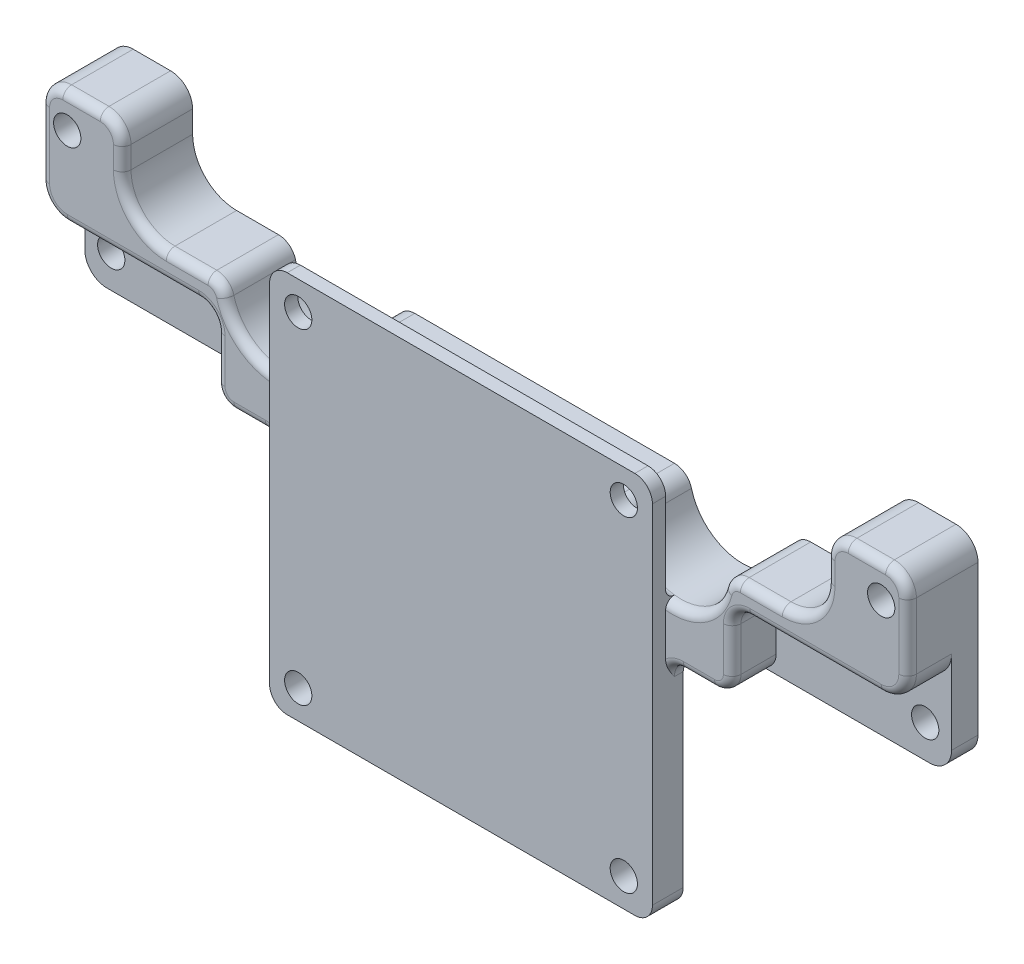
SolidWorks part; units mm, degrees
ref_plane "Front Plane" through (0, 0, 0) normal (0, 0, 1) x (1, 0, 0)
ref_plane "Top Plane" through (0, 0, 0) normal (0, 1, 0) x (1, 0, 0)
ref_plane "Right Plane" through (0, 0, 0) normal (1, 0, 0) x (0, 0, -1)
sketch "Sketch2" plane through (0, 0, 0) normal (0, 0, 1) x (1, 0, 0)
  line L0 (0, 11) -> (0, 0) construction
  line L1 (-49.25, -11) -> (49.25, -11)
  line L2 (-49.25, -11) -> (-49.25, 11)
  line L3 (-49.25, 11) -> (-40, 11)
  line L5 (-49.25, -11) -> (49.25, 11) construction
  line L6 (-49.25, 11) -> (49.25, -11) construction
  line L7 (-49.25, 0) -> (0, 0) construction
  line L8 (-46.25, 9.25) -> (-46.25, -9.25) construction
  line L9 (40, 1) -> (-40, 1)
  line L10 (-40, 1) -> (-40, 11)
  line L11 (0, 1) -> (0, 0)
  line L12 (49.25, -11) -> (49.25, 11)
  line L13 (49.25, 11) -> (40, 11)
  line L14 (40, 1) -> (40, 11)
  circle A0 centre (-46.25, 7.25) radius 2
  circle A1 centre (-46.25, -7.25) radius 2
  circle A2 centre (46.25, 7.25) radius 2
  circle A3 centre (46.25, -7.25) radius 2
  point P0 (0, 0)
  dimension "D4" = 4
  dimension "D1" = 98.5
  dimension "D2" = 22
  dimension "D3" = 18.5
  dimension "D5" = 9.25
  dimension "D6" = 3
  dimension "D7" = 40
  dimension "D8" = 10
extrude "Boss-Extrude1" add sketch "Sketch2" along normal blind 8 contours L12 L13 L14 L9 L10 L3 L2 L1 | A1 | A0 | A3 | A2
fillet "Fillet1" radius 2.5 4 edges at (-49.25, 11, 4) (-49.25, -11, 4) (49.25, 11, 4) (49.25, -11, 4)
fillet "Fillet2" radius 2.5 2 edges at (-40, 11, 4) (40, 11, 4)
fillet "Fillet3" radius 5 2 edges at (-40, 1, 4) (40, 1, 4)
sketch "Sketch4" plane through (0, 0, 8) normal (0, 0, 1) x (1, 0, 0)
  line L0 (0, -11) -> (0, 1) construction
  line L1 (-46.75, -11) -> (46.75, -11) construction
  line L2 (35, 1) -> (-35, 1) construction
  circle A0 centre (-22.5, 1) radius 6
  circle A1 centre (22.5, 1) radius 6
  dimension "D2" = 12
  dimension "D1" = 45
extrude "Cut-Extrude1" cut sketch "Sketch4" against normal blind 3
fillet "Fillet4" radius 2 4 edges at (-16.5, 1, 6.5) (16.5, 1, 6.5) (28.5, 1, 6.5) (-28.5, 1, 6.5)
sketch "Sketch6" plane through (0, 0, 8) normal (0, 0, 1) x (1, 0, 0)
  line L0 (-46.25, 7.25) -> (46.25, 7.25) construction
  line L1 (0, 7.25) -> (0, -14.5) construction
  line L3 (21.75, -36.25) -> (-21.75, -36.25)
  line L4 (21.75, -36.25) -> (21.75, 7.25)
  line L5 (21.75, 7.25) -> (-21.75, 7.25)
  line L6 (-21.75, -36.25) -> (-21.75, 7.25)
  line L7 (21.75, -36.25) -> (-21.75, 7.25) construction
  line L8 (21.75, 7.25) -> (-21.75, -36.25) construction
  dimension "D2" = 43.5
  dimension "D3" = 43.5
extrude "Boss-Extrude2" add sketch "Sketch6" along normal blind 1.5
sketch "Sketch8" plane through (0, 0, 5) normal (0, 0, 1) x (1, 0, 0)
  line L1 (30.246, 1) -> (14.754, 1)
  line L2 (30.246, 1) -> (14.754, 1)
  line L3 (-14.754, 1) -> (-30.246, 1)
  line L4 (-14.754, 1) -> (-30.246, 1)
  arc A3 (16.6905, -0.5) -> (14.754, 1) centre (14.754, -1) ccw
  arc A4 (16.6905, -0.5) -> (28.3095, -0.5) centre (22.5, 1) ccw
  arc A5 (30.246, 1) -> (28.3095, -0.5) centre (30.246, -1) ccw
  arc A6 (16.6905, -0.5) -> (14.754, 1) centre (14.754, -1) ccw
  arc A7 (16.6905, -0.5) -> (28.3095, -0.5) centre (22.5, 1) ccw
  arc A8 (30.246, 1) -> (28.3095, -0.5) centre (30.246, -1) ccw
  arc A9 (-28.3095, -0.5) -> (-30.246, 1) centre (-30.246, -1) ccw
  arc A10 (-28.3095, -0.5) -> (-16.6905, -0.5) centre (-22.5, 1) ccw
  arc A11 (-14.754, 1) -> (-16.6905, -0.5) centre (-14.754, -1) ccw
  arc A12 (-28.3095, -0.5) -> (-30.246, 1) centre (-30.246, -1) ccw
  arc A13 (-28.3095, -0.5) -> (-16.6905, -0.5) centre (-22.5, 1) ccw
  arc A14 (-14.754, 1) -> (-16.6905, -0.5) centre (-14.754, -1) ccw
  dimension "D1" = 0
  dimension "D2" = 0
extrude "Cut-Extrude2" cut sketch "Sketch8" against normal through all
sketch "Sketch7" plane through (0, 0, 9.5) normal (0, 0, 1) x (1, 0, 0)
  line L0 (0, 7.25) -> (0, -36.25) construction
  line L1 (21.75, 7.25) -> (-21.75, 7.25) construction
  line L2 (-21.75, -36.25) -> (21.75, -36.25) construction
  line L4 (18.5, -33) -> (-18.5, -33) construction
  line L5 (18.5, -33) -> (18.5, 4) construction
  line L6 (18.5, 4) -> (-18.5, 4) construction
  line L7 (-18.5, -33) -> (-18.5, 4) construction
  line L8 (18.5, -33) -> (-18.5, 4) construction
  line L9 (18.5, 4) -> (-18.5, -33) construction
  circle A0 centre (-18.5, 4) radius 1.55
  circle A1 centre (18.5, 4) radius 1.55
  circle A2 centre (18.5, -33) radius 1.55
  circle A3 centre (-18.5, -33) radius 1.55
  point P6 (0, -14.5)
  dimension "D3" = 3.1
  dimension "D1" = 37
  dimension "D2" = 37
extrude "Cut-Extrude3" cut sketch "Sketch7" against normal through all
sketch "Sketch9" plane through (0, 0, 8) normal (0, 0, -1) x (-1, 0, 0)
  line L4 (21.75, -36.25) -> (21.75, -11)
  line L5 (21.75, -11) -> (-21.75, -11)
  line L6 (-21.75, -11) -> (-21.75, -36.25)
  line L7 (-21.75, -36.25) -> (21.75, -36.25)
  line L8 (21.75, -36.25) -> (21.75, -11)
  line L9 (21.75, -11) -> (-21.75, -11)
  line L10 (-21.75, -11) -> (-21.75, -36.25)
  line L11 (-21.75, -36.25) -> (21.75, -36.25)
  circle A0 centre (18.5, -33) radius 1.55 construction
  circle A1 centre (-18.5, -33) radius 1.55 construction
  circle A2 centre (18.5, -33) radius 1.55
  circle A3 centre (-18.5, -33) radius 1.55
  dimension "D1" = 0
extrude "Boss-Extrude3" add sketch "Sketch9" along normal blind 2
fillet "Fillet5" radius 2 3 edges at (-21.75, -11, 7) (21.75, -11, 7) (0, -11, 6)
sketch "Sketch11" plane through (0, 0, 8) normal (0, 0, 1) x (1, 0, 0)
  line L1 (53.3142, -14.1394) -> (29.3142, -14.1394)
  line L2 (53.3142, -14.1394) -> (53.3142, -2.0055)
  line L3 (53.3142, -2.0055) -> (29.3142, -2.0055)
  line L4 (29.3142, -14.1394) -> (29.3142, -2.0055)
  dimension "D1" = 24
extrude "Cut-Extrude4" cut sketch "Sketch11" against normal blind 5
fillet "Fillet6" radius 2 2 edges at (29.3142, -11, 5.5) (29.3142, -2.0055, 5.5)
fillet "Fillet7" radius 3 1 edges at (49.25, -2.0055, 5.5)
fillet "Fillet8" radius 1 16 edges at (25.87, -3.9642, 8) (29.0212, 0.5811, 8) (32.623, 1, 8) (38.5355, 2.4645, 8) (40, 7.25, 8) (40.7322, 10.2678, 8) (44.625, 11, 8) (48.5178, 10.2678, 8) (49.25, 4.7473, 8) (48.3713, -1.1268, 8) (22.3358, -11.5858, 8) (25.5321, -11, 8) (28.7284, -10.4142, 8) (29.3142, -6.5027, 8) (29.9, -2.5912, 8) (38.7821, -2.0055, 8)
fillet "Fillet9" radius 2 2 edges at (21.75, 7.25, 8.75) (21.75, -36.25, 7.75)
fillet "Fillet11" radius 1 5 edges at (18.5359, -3.504, 8) (15.9788, 0.5811, 8) (-18.5359, -3.504, 8) (-15.9788, 0.5811, 8) (0, 1, 8)
sketch "Sketch13" plane through (0, 0, 9.5) normal (0, 0, 1) x (1, 0, 0)
  line L0 (-49.25, 0) -> (49.25, 0) construction
  line L1 (-49.25, -8.5) -> (-49.25, 8.5) construction
  line L2 (49.25, -8.5) -> (49.25, 0.9945) construction
  line L3 (0, 0) -> (0, 36.5553)
  line L4 (0, 36.5553) -> (-73.6778, 31.2112)
  line L5 (-73.6778, 31.2112) -> (-63.6791, -36.8835)
  line L6 (-63.6791, -36.8835) -> (-4.8936, -56.0189)
  line L7 (-4.8936, -56.0189) -> (-1.9629, -52.9159)
  line L8 (-1.9629, -52.9159) -> (0, -39.4693)
  line L9 (0, -39.4693) -> (0, 0)
extrude "Cut-Extrude5" cut sketch "Sketch13" against normal through all both and the other way through all
mirror "Mirror1" about plane through (0, 0, 0) normal (1, 0, 0) of bodies 108
sketch "Sketch14" plane through (0, 0, 8) normal (0, 0, 1) x (1, 0, 0)
  circle A0 centre (46.25, 7.25) radius 2 construction
  circle A1 centre (46.25, -7.25) radius 2 construction
  circle A2 centre (-46.25, -7.25) radius 2 construction
  circle A3 centre (-46.25, 7.25) radius 2 construction
  circle A4 centre (46.25, 7.25) radius 2
  circle A5 centre (46.25, -7.25) radius 2
  circle A6 centre (-46.25, -7.25) radius 2
  circle A7 centre (-46.25, 7.25) radius 2
  circle A8 centre (46.25, 7.25) radius 1.55
  circle A9 centre (46.25, -7.25) radius 1.55
  circle A10 centre (-46.25, 7.25) radius 1.55
  circle A11 centre (-46.25, -7.25) radius 1.55
  dimension "D2" = 0.45
  dimension "D1" = 0.45
  dimension "D3" = 0.45
  dimension "D4" = 0.45
extrude "Boss-Extrude4" add sketch "Sketch14" against normal up to surface (8 mm away) up to face at (44.25, 7.25, 0)
sketch "Sketch15" plane through (0, 0, 3) normal (0, 0, 1) x (1, 0, 0)
  line L1 (-61.4753, -2.8637) -> (-35.6183, -2.8637)
  line L2 (-61.4753, -2.8637) -> (-61.4753, -19.0633)
  line L3 (-61.4753, -19.0633) -> (-35.6183, -19.0633)
  line L4 (-35.6183, -2.8637) -> (-35.6183, -19.0633)
  line L5 (54.5178, -21.5555) -> (37.1759, -21.5555)
  line L6 (54.5178, -21.5555) -> (54.5178, -4.4214)
  line L7 (54.5178, -4.4214) -> (37.1759, -4.4214)
  line L8 (37.1759, -21.5555) -> (37.1759, -4.4214)
extrude "Cut-Extrude6" cut sketch "Sketch15" along normal through all
